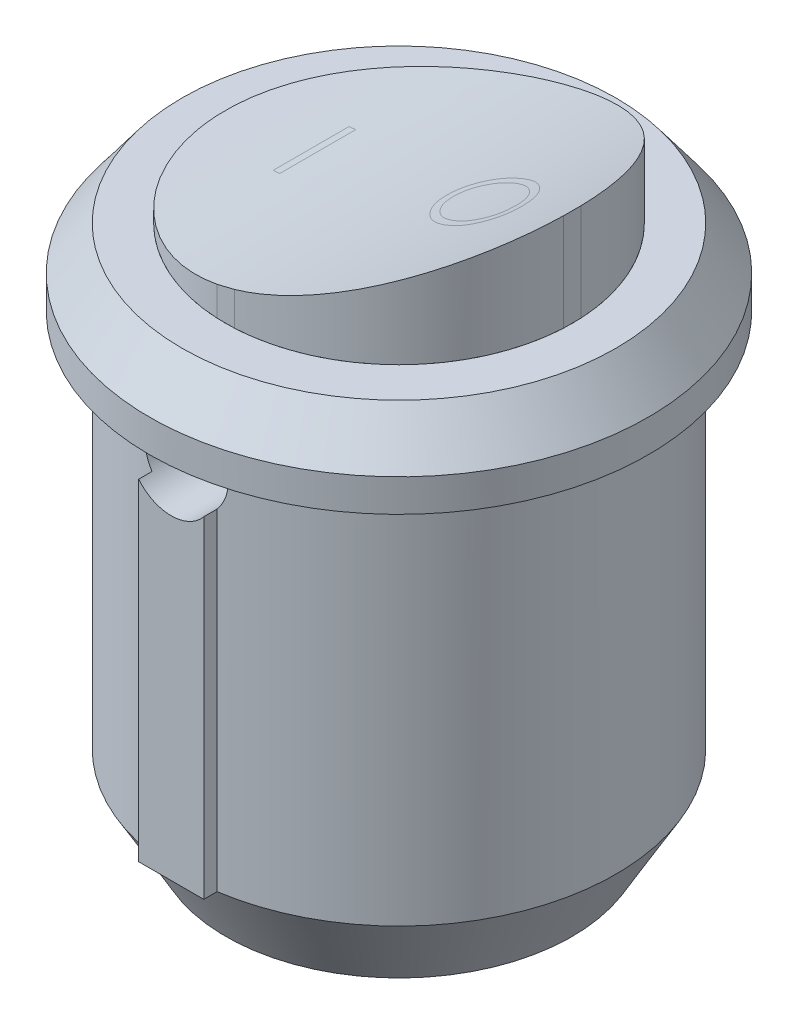
SolidWorks part; units mm, degrees
ref_plane "Front Plane" through (0, 0, 0) normal (0, 0, 1) x (1, 0, 0)
ref_plane "Top Plane" through (0, 0, 0) normal (0, 1, 0) x (1, 0, 0)
ref_plane "Right Plane" through (0, 0, 0) normal (1, 0, 0) x (0, 0, -1)
sketch "Sketch1" plane through (0, 0, 0) normal (0, 1, 0) x (1, 0, 0)
  circle A0 centre (0, 0) radius 11.5
  dimension "D1" = 23
extrude "Boss-Extrude1" add sketch "Sketch1" along normal blind 1.5
sketch "Sketch2" plane through (0, 1.5, 0) normal (0, 1, 0) x (1, 0, 0)
  circle A0 centre (0, 0) radius 11.5
ref_plane "Plane1" through (0, 3.5, 0) normal (0, 1, 0) x (1, 0, 0)
sketch "Sketch5" plane through (0, 3.5, 0) normal (0, 1, 0) x (1, 0, 0)
  circle A0 centre (0, 0) radius 10
loft "Loft1" add profiles "Sketch2", "Sketch5" connector at (-11.0633, 1.5, 3.1389) connector at (-9.8709, 3.5, 1.6016)
sketch "Sketch6" plane through (0, 3.5, 0) normal (0, 1, 0) x (1, 0, 0)
  circle A0 centre (0, 0) radius 8
extrude "Cut-Extrude1" cut sketch "Sketch6" against normal blind 1
fillet "Fillet2" radius 2 1 edges at (0, 2.5, 8)
sketch "Sketch7" plane through (0, 0, 0) normal (0, 0, 1) x (1, 0, 0)
  line L0 (0, 3.5) -> (-7.99, 3.5)
  line L1 (10, 3.5) -> (-10, 3.5) construction
  line L2 (0, 3.5) -> (7.99, 3.5)
  line L3 (-7.99, 3.5) -> (-7.99, 4)
  line L4 (7.99, 7.9891) -> (7.99, 3.5)
  spline S0 degree 2 poles (-7.99, 4) (0.4852, 4.0195) (7.99, 7.9891) knots 0 0 0 1 1 1
  dimension "D1" = 0.5
  dimension "D2" = 7.99
  dimension "D3" = 7.99
extrude "Boss-Extrude7" add sketch "Sketch7" along normal blind 7.99 and the other way blind 7.99
sketch "Sketch8" plane through (0, 3.5, 0) normal (0, 1, 0) x (1, 0, 0)
  circle A0 centre (0, 0) radius 8
  circle A1 centre (0, 0) radius 11.5
extrude "Cut-Extrude3" cut sketch "Sketch8" along normal blind 7.99
ref_plane "Plane2" through (0, 7.9891, 0) normal (0, 1, 0) x (1, 0, 0)
sketch "Sketch10" plane through (0, 7.9891, 0) normal (0, 1, 0) x (1, 0, 0)
  line L0 (-4.8433, -1.5) -> (4.8113, -1.5) construction
  text T0 "I    O"
  dimension "D1" = 1.5
wrap "Wrap1" sketch "Sketch10" wrap type scribe source sketch "Sketch10" face at (0.1575, 5.5186, -0.0198)
sketch "Sketch13" plane through (0, 0, 0) normal (0, -1, 0) x (1, 0, 0)
  circle A0 centre (0, 0) radius 10
  dimension "D1" = 20
extrude "Boss-Extrude8" add sketch "Sketch13" along normal blind 21
sketch "Sketch16" plane through (0, -21, 0) normal (0, -1, 0) x (1, 0, 0)
  line L7 (-1.5, -10.5) -> (1.5, -10.5)
  line L8 (-1.5, -10.5) -> (-1.5, 10.5)
  line L9 (-1.5, 10.5) -> (1.5, 10.5)
  line L10 (1.5, -10.5) -> (1.5, 10.5)
  line L11 (-1.5, -10.5) -> (1.5, 10.5) construction
  line L12 (-1.5, 10.5) -> (1.5, -10.5) construction
  point P0 (0, 0)
  point P6 (0, 0)
  dimension "D3" = 21
  dimension "D4" = 3
extrude "Boss-Extrude9" add sketch "Sketch16" against normal blind 21
sketch "Sketch17" plane through (0, 0, 10.5) normal (0, 0, 1) x (1, 0, 0)
  line L0 (0, 0) -> (0, -1) construction
  line L4 (-10, 0) -> (-1.5, 0) construction
  line L5 (-1.6583, 0) -> (1.6583, 0)
  arc A0 (-1.6583, 0) -> (1.6583, 0) centre (0, -1) ccw
  dimension "D1" = 1
extrude "Cut-Extrude4" cut sketch "Sketch17" against normal through all
sketch "Sketch20" plane through (0, -21, 0) normal (0, -1, 0) x (1, 0, 0)
  line L0 (-1.5, 9.8869) -> (-1.5, 10.5)
  line L1 (-1.5, -10.5) -> (1.5, -10.5)
  line L2 (-1.5, -10.5) -> (-1.5, -9.8869)
  line L3 (-1.5, 10.5) -> (1.5, 10.5)
  line L4 (1.5, -10.5) -> (1.5, -9.8869)
  line L5 (-1.5, -10.5) -> (-1.4142, -9.8995) construction
  line L6 (-1.5, 10.5) -> (-1.4142, 9.8995) construction
  line L7 (1.4142, -9.8995) -> (1.5, -10.5) construction
  line L8 (1.4142, 9.8995) -> (1.5, 10.5) construction
  line L9 (1.5, 9.8869) -> (1.5, 10.5)
  arc A0 (-1.5, 9.8869) -> (1.5, 9.8869) centre (0, 0) cw
  arc A1 (-1.5, -9.8869) -> (1.5, -9.8869) centre (0, 0) ccw
  arc A2 (1.5, -9.8869) -> (1.5, 9.8869) centre (0, 0) ccw construction
  point P0 (0, 0)
extrude "Cut-Extrude5" cut sketch "Sketch20" against normal blind 3.5
chamfer "Chamfer1" distance 3.5 angle 30 1 edges at (0, -21, -10) first distance on face at (0, -6.5819, 0)
